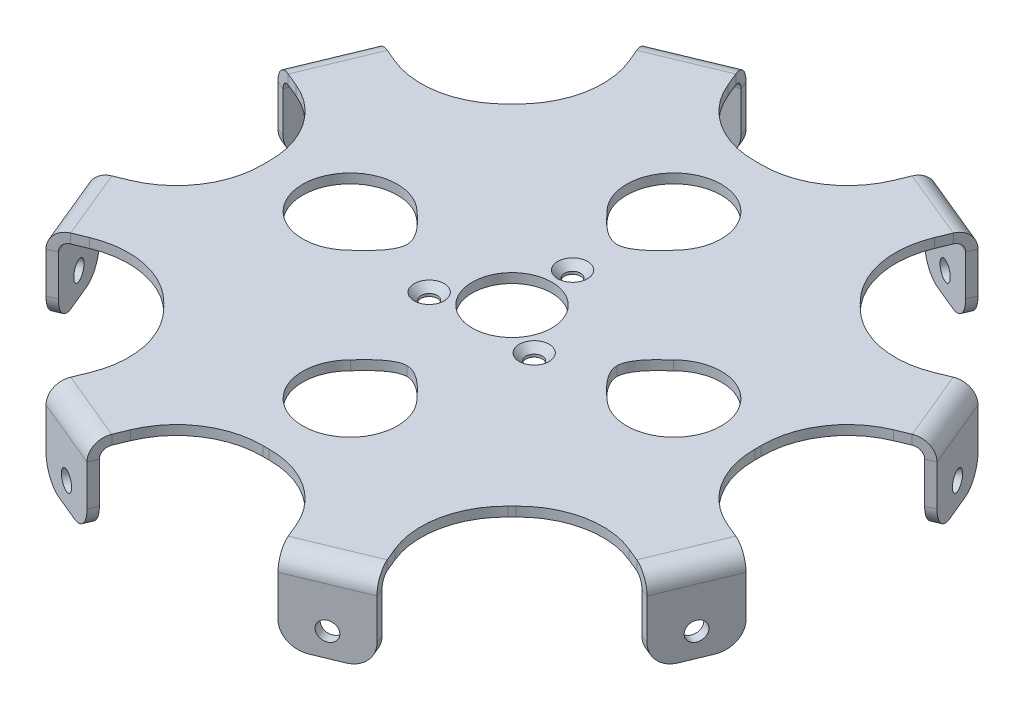
SolidWorks part; units mm, degrees
note: The reader was unsure of these and kept them because the rebuilt part matched: flange length of "Kante-Lasche1".
ref_plane "Ebene vorne" through (0, 0, 0) normal (0, 0, 1) x (1, 0, 0)
ref_plane "Ebene oben" through (0, 0, 0) normal (0, 1, 0) x (1, 0, 0)
ref_plane "Ebene rechts" through (0, 0, 0) normal (1, 0, 0) x (0, 0, -1)
sketch "Skizze1" plane through (0, 0, 0) normal (0, 1, 0) x (1, 0, 0)
  line L0 (0, 0) -> (-146.7259, 60.7759) construction
  line L1 (0, 16) -> (0, 0) construction
  line L2 (-79.3223, 43.6803) -> (-86.976, 25.2027)
  line L3 (-86.976, 25.2027) -> (-78.8832, 21.8506)
  line L4 (-79.3223, 43.6803) -> (-71.2295, 40.3281)
  line L6 (-25.2027, 86.976) -> (-43.6803, 79.3223)
  line L7 (-43.6803, 79.3223) -> (-40.3281, 71.2295)
  line L8 (-25.2027, 86.976) -> (-21.8506, 78.8832)
  line L9 (43.6803, 79.3223) -> (25.2027, 86.976)
  line L10 (25.2027, 86.976) -> (21.8506, 78.8832)
  line L11 (43.6803, 79.3223) -> (40.3281, 71.2295)
  line L12 (86.976, 25.2027) -> (79.3223, 43.6803)
  line L13 (79.3223, 43.6803) -> (71.2295, 40.3281)
  line L14 (86.976, 25.2027) -> (78.8832, 21.8506)
  line L15 (79.3223, -43.6803) -> (86.976, -25.2027)
  line L16 (86.976, -25.2027) -> (78.8832, -21.8506)
  line L17 (79.3223, -43.6803) -> (71.2295, -40.3281)
  line L18 (25.2027, -86.976) -> (43.6803, -79.3223)
  line L19 (43.6803, -79.3223) -> (40.3281, -71.2295)
  line L20 (25.2027, -86.976) -> (21.8506, -78.8832)
  line L21 (-43.6803, -79.3223) -> (-25.2027, -86.976)
  line L22 (-25.2027, -86.976) -> (-21.8506, -78.8832)
  line L23 (-43.6803, -79.3223) -> (-40.3281, -71.2295)
  line L24 (-86.976, -25.2027) -> (-79.3223, -43.6803)
  line L25 (-79.3223, -43.6803) -> (-71.2295, -40.3281)
  line L26 (-86.976, -25.2027) -> (-78.8832, -21.8506)
  line L27 (0, 0) -> (0, 22.5) construction
  line L30 (8.7998, -33.8723) -> (8.8005, -33.8723)
  line L31 (-33.8723, -8.7998) -> (-33.8723, -8.8005)
  line L32 (-8.7998, 33.8723) -> (-8.8005, 33.8723)
  line L33 (33.8723, 8.7998) -> (33.8723, 8.8005)
  circle A0 centre (0, 0) radius 10.5
  arc A1 (-64.9952, 0.7899) -> (-64.9952, -0.7899) centre (0, 0) ccw
  circle A2 centre (0, 16) radius 2.15
  circle A3 centre (13.8564, -8) radius 2.15
  circle A4 centre (-13.8564, -8) radius 2.15
  arc A5 (-71.2295, 40.3281) -> (-46.5171, 45.4) centre (-62.6191, 61.1154) ccw
  arc A6 (-78.8832, 21.8506) -> (-64.9952, 0.7899) centre (-87.4935, 1.0633) cw
  arc A7 (-21.8506, 78.8832) -> (-0.7899, 64.9952) centre (-1.0633, 87.4935) ccw
  arc A8 (-40.3281, 71.2295) -> (-45.4, 46.5171) centre (-61.1154, 62.6191) cw
  arc A9 (40.3281, 71.2295) -> (45.4, 46.5171) centre (61.1154, 62.6191) ccw
  arc A10 (21.8506, 78.8832) -> (0.7899, 64.9952) centre (1.0633, 87.4935) cw
  arc A11 (78.8832, 21.8506) -> (64.9952, 0.7899) centre (87.4935, 1.0633) ccw
  arc A12 (71.2295, 40.3281) -> (46.5171, 45.4) centre (62.6191, 61.1154) cw
  arc A13 (71.2295, -40.3281) -> (46.5171, -45.4) centre (62.6191, -61.1154) ccw
  arc A14 (78.8832, -21.8506) -> (64.9952, -0.7899) centre (87.4935, -1.0633) cw
  arc A15 (21.8506, -78.8832) -> (0.7899, -64.9952) centre (1.0633, -87.4935) ccw
  arc A16 (40.3281, -71.2295) -> (45.4, -46.5171) centre (61.1154, -62.6191) cw
  arc A17 (-40.3281, -71.2295) -> (-45.4, -46.5171) centre (-61.1154, -62.6191) ccw
  arc A18 (-21.8506, -78.8832) -> (-0.7899, -64.9952) centre (-1.0633, -87.4935) cw
  arc A19 (-78.8832, -21.8506) -> (-64.9952, -0.7899) centre (-87.4935, -1.0633) ccw
  arc A20 (-71.2295, -40.3281) -> (-46.5171, -45.4) centre (-62.6191, -61.1154) cw
  arc A21 (-45.4, 46.5171) -> (-46.5171, 45.4) centre (0, 0) ccw
  arc A22 (0.7899, 64.9952) -> (-0.7899, 64.9952) centre (0, 0) ccw
  arc A23 (46.5171, 45.4) -> (45.4, 46.5171) centre (0, 0) ccw
  arc A24 (64.9952, -0.7899) -> (64.9952, 0.7899) centre (0, 0) ccw
  arc A25 (45.4, -46.5171) -> (46.5171, -45.4) centre (0, 0) ccw
  arc A26 (-0.7899, -64.9952) -> (0.7899, -64.9952) centre (0, 0) ccw
  arc A27 (-46.5171, -45.4) -> (-45.4, -46.5171) centre (0, 0) ccw
  arc A30 (-8.7998, -33.8723) -> (8.7998, -33.8723) centre (0, -42.75) ccw
  arc A31 (-33.8723, 8.7998) -> (-33.8723, -8.7998) centre (-42.75, 0) ccw
  arc A32 (8.7998, 33.8723) -> (-8.7998, 33.8723) centre (0, 42.75) ccw
  arc A33 (33.8723, -8.7998) -> (33.8723, 8.7998) centre (42.75, 0) ccw
  spline S0 degree 2 poles (0.0003, -27.7027) (-3.3891, -27.7027) (-8.7998, -33.8723) knots 0 0 0 1 1 1
  spline S1 degree 2 poles (0.0003, -27.7027) (3.3897, -27.7027) (8.8005, -33.8723) knots 0 0 0 1 1 1
  spline S2 degree 2 poles (-27.7027, -0.0003) (-27.7027, 3.3891) (-33.8723, 8.7998) knots 0 0 0 1 1 1
  spline S3 degree 2 poles (-27.7027, -0.0003) (-27.7027, -3.3897) (-33.8723, -8.8005) knots 0 0 0 1 1 1
  spline S4 degree 2 poles (-0.0003, 27.7027) (3.3891, 27.7027) (8.7998, 33.8723) knots 0 0 0 1 1 1
  spline S5 degree 2 poles (-0.0003, 27.7027) (-3.3897, 27.7027) (-8.8005, 33.8723) knots 0 0 0 1 1 1
  spline S6 degree 2 poles (27.7027, 0.0003) (27.7027, -3.3891) (33.8723, -8.7998) knots 0 0 0 1 1 1
  spline S7 degree 2 poles (27.7027, 0.0003) (27.7027, 3.3897) (33.8723, 8.8005) knots 0 0 0 1 1 1
  point P13 (0, 0)
  point P17 (-83.1492, 34.4415)
  point P18 (-55.5104, 33.8171)
  point P21 (-63.1641, 15.3395)
  point P24 (0, -42.75)
  point P33 (-34.4415, 83.1492)
  point P42 (34.4415, 83.1492)
  point P51 (83.1492, 34.4415)
  point P60 (83.1492, -34.4415)
  point P69 (34.4415, -83.1492)
  point P78 (-34.4415, -83.1492)
  point P87 (-83.1492, -34.4415)
  point P90 (0, 0)
  point P95 (0, -42.75)
  point P98 (-42.75, 0)
  point P102 (-42.75, 0)
  point P105 (0, 42.75)
  point P109 (0, 42.75)
  point P110 (0, 0)
  point P113 (42.75, 0)
  point P118 (42.75, 0)
  point P121 (0, 0)
  dimension "D1" = 21
  dimension "D2" = 130
  dimension "D3" = 4.3
  dimension "D8" = 22.5
  dimension "D11" = 4
  dimension "D4" = 16
  dimension "D6" = 67.5
  dimension "D7" = 10
  dimension "D9" = 90
  dimension "D5" = 3
  dimension "D10" = 8
base flange "Basis-Blech1" sketch "Skizze1" thickness 2.5 reverse thickness direction no parameters "D1"=3
edge flange "Kante-Lasche1" sketch "Skizze4" flange angle 90 flange length 22 flange position material inside bend radius 2.5 thickness 2.5 relief rectangular parameters "D6"=10
sketch "Skizze4" plane through (-83.1492, -2.5, -34.4415) normal (0.9239, 0, 0.3827) x (-0.3827, 0, 0.9239)
  line L2 (-10, 0) -> (-10, 19.5)
  line L3 (-10, 19.5) -> (10, 19.5)
  line L4 (10, 19.5) -> (10, 0)
  line L5 (10, 0) -> (-10, 0) construction
  line L6 (10, 0) -> (-10, 0)
bend "Kantenbiegung1" bend radius 2.5 bend angle 90 parameters "D5"=1
sketch "Skizze5" plane through (-83.1492, 0, -34.4415) normal (-0.9239, 0, -0.3827) x (-0.3827, 0, 0.9239)
  line L2 (10, -22) -> (-10, -22) construction
  circle A0 centre (0, -15.75) radius 2.5
  point P5 (0, -22)
  dimension "D1" = 5
  dimension "D2" = 0
  dimension "D3" = 6.25
extrude "Schnitt-Linear austragen1" cut sketch "Skizze5" against normal through all normal cut yes
fillet "Verrundung1" radius 6.25 2 edges at (-85.8211, -22, -24.7244) (-78.1675, -22, -43.2019)
pattern_circular "Kreismuster1" count 8 every 45 about axis through (0, 0, 0) along (0, 1, 0) of "Kante-Lasche1", "Schnitt-Linear austragen1", "Verrundung1"
bend "KreisMusterBiegung1" bend radius 2.5 bend angle 90 parameters "D5"=2
bend "KreisMusterBiegung2" bend radius 2.5 bend angle 90 parameters "D5"=3
bend "KreisMusterBiegung3" bend radius 2.5 bend angle 90 parameters "D5"=4
bend "KreisMusterBiegung4" bend radius 2.5 bend angle 90 parameters "D5"=5
bend "KreisMusterBiegung5" bend radius 2.5 bend angle 90 parameters "D5"=6
bend "KreisMusterBiegung6" bend radius 2.5 bend angle 90 parameters "D5"=7
bend "KreisMusterBiegung7" bend radius 2.5 bend angle 90 parameters "D5"=8
chamfer "Fase1" distance 1.8 angle 45 3 edges at (-13.8564, 0, 10.15) (13.8564, 0, 10.15) (0, 0, -13.85)
sketch "Biegung-Linien1" [suppressed] plane through (0, 0, 0) normal (0, 1, 0) x (1, 0, 0)
sketch "Rahmen1" [suppressed] plane through (0, 0, 0) normal (0, 1, 0) x (1, 0, 0)
sheet metal parameters "Blech1" thickness 2.5 parameters "D1"=3
flat pattern "Abwicklung1" [suppressed]
sketch "Biegung-Linien2" plane through (0, 0, 0) normal (0, 1, 0) x (1, 0, 0)
sketch3d "Rahmen2" [suppressed]
  line L0 (-44.6737, 0.5908, 0) -> (32.951, -99.9673, 0) construction
  line L1 (34.485, 61.6964, 0) -> (112.1097, -38.8617, 0) construction
  line L2 (-44.6737, 0.5908, 0) -> (34.485, 61.6964, 0) construction
  line L3 (32.951, -99.9673, 0) -> (112.1097, -38.8617, 0) construction
sheet metal parameters "Blech2" thickness 2.5 parameters "D1"=3
flat pattern "Abwicklung1"
sketch "Biegung-Linien2" plane through (0, 0, 0) normal (0, 1, 0) x (1, 0, 0)
  line L0 (-72.8046, 40.9806) -> (-80.4582, 22.503) construction
  line L1 (-72.8046, 40.9806) -> (-80.4582, 22.503) construction
sketch3d "Rahmen2" [suppressed]
  line L0 (-58.8605, 4.8115, 0) -> (39.5993, -100.5058, 0) construction
  line L1 (14.1883, 73.104, 0) -> (112.6482, -32.2134, 0) construction
  line L2 (-58.8605, 4.8115, 0) -> (14.1883, 73.104, 0) construction
  line L3 (39.5993, -100.5058, 0) -> (112.6482, -32.2134, 0) construction
bend of the flat pattern "Abwickeln-<Kantenbiegung1>1"
sheet metal parameters "Blech3" thickness 2.5 parameters "D1"=3
flat pattern "Abwicklung1"
sketch "Biegung-Linien2" plane through (0, 0, 0) normal (0, 1, 0) x (1, 0, 0)
  line L0 (-72.8046, 40.9806) -> (-80.4582, 22.503) construction
  line L1 (-72.8046, 40.9806) -> (-80.4582, 22.503) construction
sketch3d "Rahmen2" [suppressed]
  line L0 (-54.0216, -10.0953, 0) -> (11.0346, -167.1548, 0) construction
  line L1 (103.0379, 54.9609, 0) -> (168.0941, -102.0986, 0) construction
  line L2 (-54.0216, -10.0953, 0) -> (103.0379, 54.9609, 0) construction
  line L3 (11.0346, -167.1548, 0) -> (168.0941, -102.0986, 0) construction
bend of the flat pattern "Abwickeln-<Kantenbiegung1>1"
sheet metal parameters "Blech4" thickness 2.5 parameters "D1"=3
flat pattern "Abwicklung1"
sketch "Biegung-Linien2" plane through (0, 0, 0) normal (0, 1, 0) x (1, 0, 0)
  line L0 (-77.424, 42.894) -> (-85.0776, 24.4164) construction
  line L1 (-77.424, 42.894) -> (-85.0776, 24.4164) construction
  line L2 (-24.4164, 85.0776) -> (-42.894, 77.424) construction
  line L3 (42.894, 77.424) -> (24.4164, 85.0776) construction
  line L4 (85.0776, 24.4164) -> (77.424, 42.894) construction
  line L5 (77.424, -42.894) -> (85.0776, -24.4164) construction
  line L6 (24.4164, -85.0776) -> (42.894, -77.424) construction
  line L7 (-42.894, -77.424) -> (-24.4164, -85.0776) construction
  line L8 (-85.0776, -24.4164) -> (-77.424, -42.894) construction
  line L9 (-24.4164, 85.0776) -> (-42.894, 77.424) construction
  line L10 (42.894, 77.424) -> (24.4164, 85.0776) construction
  line L11 (85.0776, 24.4164) -> (77.424, 42.894) construction
  line L12 (77.424, -42.894) -> (85.0776, -24.4164) construction
  line L13 (24.4164, -85.0776) -> (42.894, -77.424) construction
  line L14 (-42.894, -77.424) -> (-24.4164, -85.0776) construction
  line L15 (-85.0776, -24.4164) -> (-77.424, -42.894) construction
sketch3d "Rahmen2" [suppressed]
  line L0 (-81.0487, -61.1153, 0) -> (62.619, -204.7833, 0) construction
  line L1 (62.6192, 82.5524, 0) -> (206.2869, -61.1156, 0) construction
  line L2 (-81.0487, -61.1153, 0) -> (62.6192, 82.5524, 0) construction
  line L3 (62.619, -204.7833, 0) -> (206.2869, -61.1156, 0) construction
bend of the flat pattern "Abwickeln-<Kantenbiegung1>1"
bend of the flat pattern "Abwickeln-<KreisMusterBiegung1>1"
bend of the flat pattern "Abwickeln-<KreisMusterBiegung2>1"
bend of the flat pattern "Abwickeln-<KreisMusterBiegung3>1"
bend of the flat pattern "Abwickeln-<KreisMusterBiegung4>1"
bend of the flat pattern "Abwickeln-<KreisMusterBiegung5>1"
bend of the flat pattern "Abwickeln-<KreisMusterBiegung6>1"
bend of the flat pattern "Abwickeln-<KreisMusterBiegung7>1"
